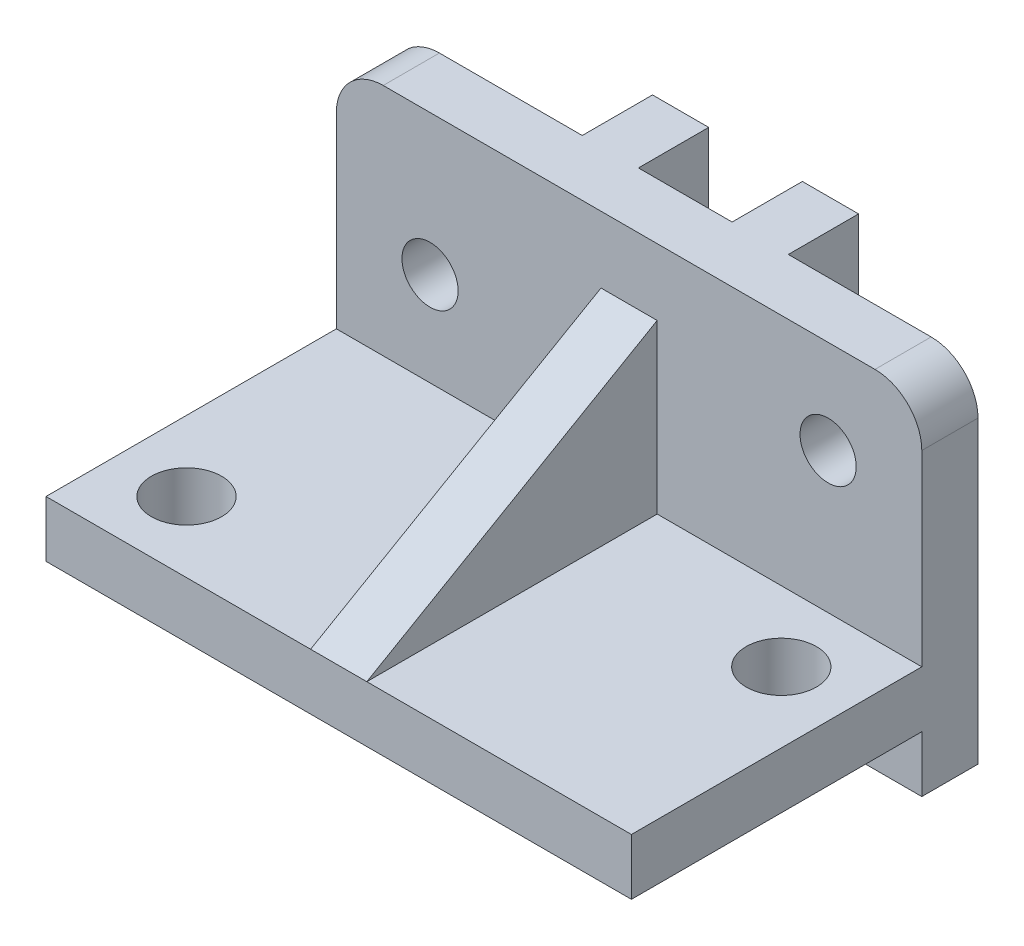
SolidWorks part; units mm, degrees
ref_plane "Front Plane" through (0, 0, 0) normal (0, 0, 1) x (1, 0, 0)
ref_plane "Top Plane" through (0, 0, 0) normal (0, 1, 0) x (1, 0, 0)
ref_plane "Right Plane" through (0, 0, 0) normal (1, 0, 0) x (0, 0, -1)
sketch "Sketch1" plane through (0, 0, 0) normal (0, 1, 0) x (1, 0, 0)
  line L0 (0, 62) -> (0, 74)
  line L1 (0, 0) -> (125, 0)
  line L2 (0, 0) -> (0, 62)
  line L3 (0, 62) -> (125, 62)
  line L4 (125, 0) -> (125, 62)
  line L5 (0, 74) -> (125, 74)
  line L6 (125, 74) -> (125, 62)
  circle A0 centre (15, 15) radius 7.5
  circle A1 centre (110, 47) radius 7.5
  dimension "D3" = 15
  dimension "D4" = 15
  dimension "D1" = 125
  dimension "D2" = 62
  dimension "D5" = 15
  dimension "D6" = 15
  dimension "D7" = 15
  dimension "D8" = 15
  dimension "D9" = 12
extrude "Boss-Extrude2" add sketch "Sketch1" along normal blind 12 contours L1 L4 L3 L2 A1 A0 region at (62.5, 0, -31)
extrude "Boss-Extrude3" add sketch "Sketch1<3>" along normal blind 62 contours L6 L5 L0 L3 region at (62.5, 0, -68)
sketch "Sketch1<3>" plane through (0, 0, 0) normal (0, 1, 0) x (1, 0, 0) same geometry as "Sketch1"
extrude "Boss-Extrude4" add sketch "Sketch1<4>" against normal blind 12 contours L6 L5 L0 L3 region at (62.5, 0, -68)
sketch "Sketch1<4>" plane through (0, 0, 0) normal (0, 1, 0) x (1, 0, 0) same geometry as "Sketch1"
sketch "Sketch3" plane through (0, 0, -62) normal (0, 0, 1) x (1, 0, 0)
  line L0 (125, 62) -> (125, 12) construction
  line L1 (0, 62) -> (125, 62) construction
  line L2 (115, 62) -> (125, 62)
  line L3 (125, 62) -> (125, 52)
  line L4 (62.5, 79.1655) -> (62.5, -28.0751) construction
  line L5 (0, 62) -> (0, 12) construction
  line L6 (0, 62) -> (0, 52)
  line L7 (10, 62) -> (0, 62)
  line L8 (0, 12) -> (125, 12) construction
  arc A0 (125, 52) -> (115, 62) centre (115, 52) ccw
  arc A1 (0, 52) -> (10, 62) centre (10, 52) cw
  circle A2 centre (105, 42) radius 6
  circle A3 centre (20, 32) radius 6
  dimension "D1" = 20
  dimension "D3" = 12
  dimension "D4" = 12
  dimension "D2" = 62.5
  dimension "D5" = 30
  dimension "D6" = 20
  dimension "D7" = 30
  dimension "D8" = 20
extrude "Cut-Extrude1" cut sketch "Sketch3" against normal up to next
sketch "Sketch4" plane through (0, 0, -74) normal (0, 0, -1) x (-1, 0, 0)
  line L0 (-84.5, 62) -> (-84.5, -12)
  line L1 (-10, 62) -> (-115, 62) construction
  line L2 (0, -12) -> (-125, -12) construction
  line L3 (-72.5, 62) -> (-72.5, -12)
  line L4 (-52.5, 62) -> (-52.5, -12)
  line L5 (-40.5, 62) -> (-40.5, -12)
  line L6 (-125, 52) -> (-125, -12) construction
  line L7 (-84.5, 62) -> (-72.5, 62)
  line L8 (-84.5, -12) -> (-72.5, -12)
  line L9 (-52.5, 62) -> (-40.5, 62)
  line L10 (-52.5, -12) -> (-40.5, -12)
  dimension "D1" = 12
  dimension "D2" = 12
  dimension "D3" = 20
  dimension "D4" = 40.5
extrude "Boss-Extrude5" add sketch "Sketch4" along normal blind 15
sketch "Sketch5" plane through (0, 12, 0) normal (0, 1, 0) x (1, 0, 0)
  line L0 (56.5, 0) -> (56.5, 62)
  line L1 (0, 0) -> (125, 0) construction
  line L2 (0, 62) -> (125, 62) construction
  line L3 (68.5, 62) -> (68.5, 0)
  line L4 (0, 0) -> (0, 62) construction
  line L6 (56.5, 62) -> (68.5, 62)
  line L7 (56.5, 0) -> (68.5, 0)
  dimension "D1" = 12
  dimension "D2" = 56.5
extrude "Boss-Extrude6" add sketch "Sketch5" along normal blind 50
sketch "Sketch6" plane through (68.5, 0, 0) normal (1, 0, 0) x (0, 0, -1)
  line L2 (0, 12) -> (62, 47.7957)
  line L3 (62, 62) -> (62, 12) construction
  line L5 (0, 12) -> (0, 62)
  line L6 (0, 62) -> (62, 62)
  line L7 (62, 62) -> (62, 47.7957)
extrude "Cut-Extrude2" cut sketch "Sketch6" against normal up to next
